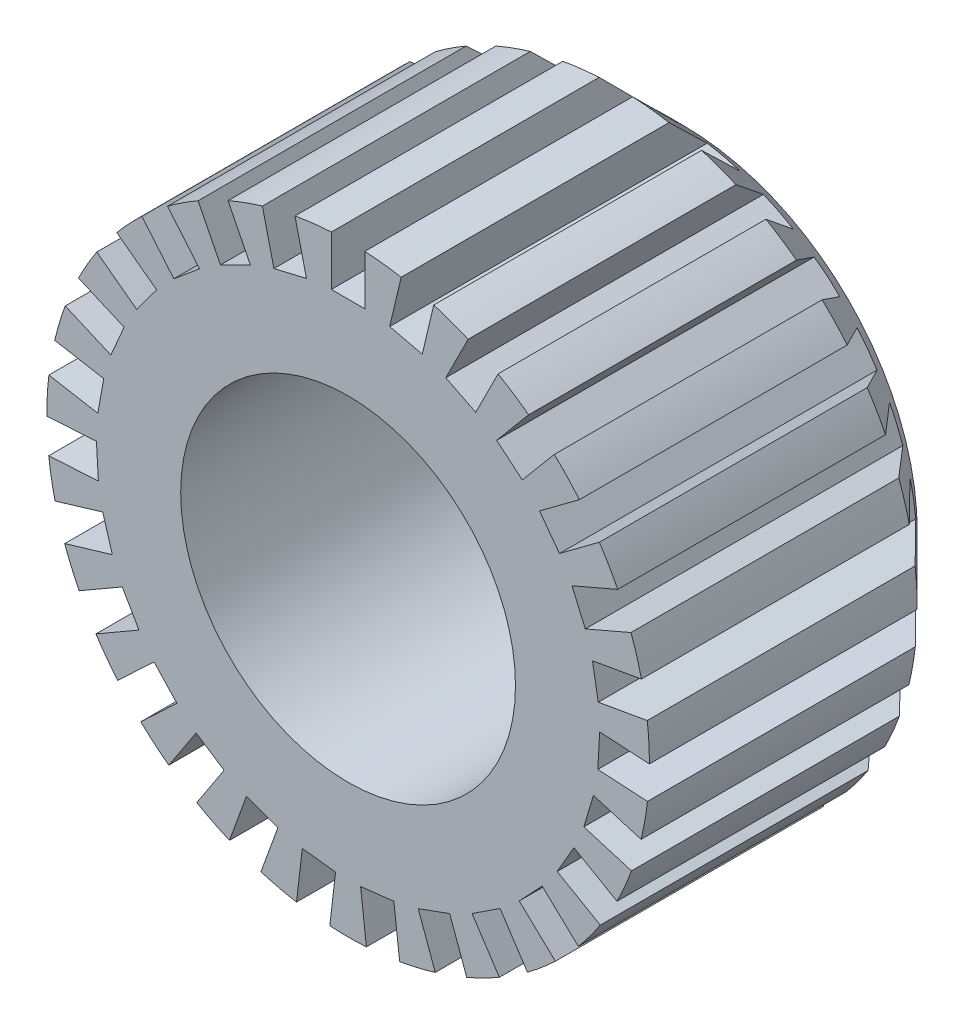
SolidWorks part; units mm, degrees
ref_plane "Front Plane" through (0, 0, 0) normal (0, 0, 1) x (1, 0, 0)
ref_plane "Top Plane" through (0, 0, 0) normal (0, 1, 0) x (1, 0, 0)
ref_plane "Right Plane" through (0, 0, 0) normal (1, 0, 0) x (0, 0, -1)
sketch "Sketch1" plane through (0, 0, 0) normal (0, 0, 1) x (1, 0, 0)
  circle A0 centre (0, 0) radius 5
  circle A1 centre (0, 0) radius 9
  dimension "D1" = 18
  dimension "D2" = 10
extrude "Boss-Extrude1" add sketch "Sketch1" along normal blind 10
chamfer "Chamfer1" distance 2 angle 45 1 edges at (9, 0, 0)
ref_axis "Axis1" through (0, 0, 10) along (0, 0, -1)
sketch "Sketch2" plane through (0, 0, 0) normal (0, 0, -1) x (-1, 0, 0)
  line L0 (-0.5, 7.5) -> (0.5, 7.5)
  line L1 (0, 0) -> (0, 10.6556) construction
  line L2 (0.5, 7.5) -> (0.5, 8.9861)
  line L3 (-0.5, 7.5) -> (-0.5, 8.9861)
  arc A0 (0.5, 8.9861) -> (-0.5, 8.9861) centre (0, 0) ccw
  point P5 (0, 7.5)
  dimension "D1" = 7.5
  dimension "D2" = 1
extrude "Cut-Extrude1" cut sketch "Sketch2" against normal through all
pattern_circular "CirPattern1" count 27 over 360 about axis through (0, 0, 10) along (0, 0, -1) of "Cut-Extrude1"
